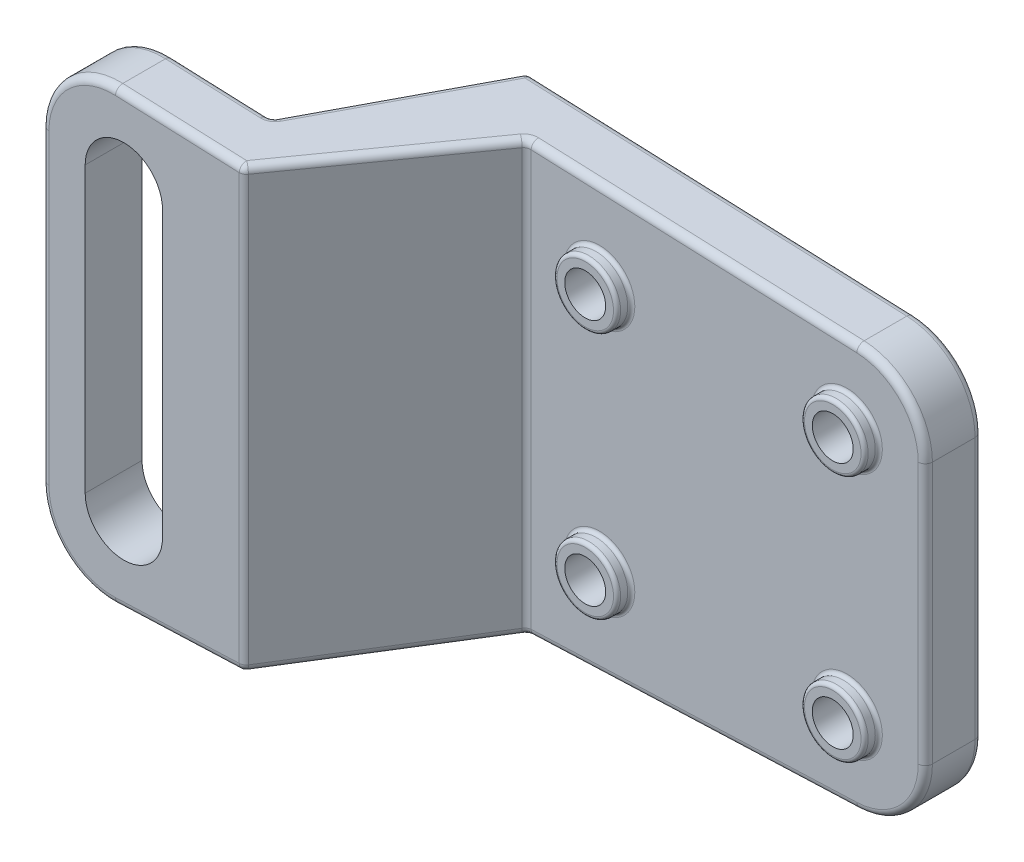
SolidWorks part; units mm, degrees
ref_plane "Front Plane" through (0, 0, 0) normal (0, 0, 1) x (1, 0, 0)
ref_plane "Top Plane" through (0, 0, 0) normal (0, 1, 0) x (1, 0, 0)
ref_plane "Right Plane" through (0, 0, 0) normal (1, 0, 0) x (0, 0, -1)
sketch "Sketch1" plane through (0, 0, 0) normal (0, 0, 1) x (1, 0, 0)
  line L0 (0, 0) -> (13.8229, 0) construction
  line L1 (13.8229, 0) -> (13.8229, -13.8229) construction
  line L2 (13.8229, -13.8229) -> (0, -13.8229) construction
  line L3 (0, -13.8229) -> (0, 0) construction
  line L4 (-17.0322, 1.026) -> (-17.0322, -14.849) construction
  line L5 (-17.0322, 1.026) -> (-17.0322, -14.849) construction
  line L6 (-14.8732, 1.026) -> (-14.8732, -14.849)
  line L7 (-19.1912, 1.026) -> (-19.1912, -14.849)
  line L8 (13.8229, 4.3755) -> (13.8229, 0) construction
  line L9 (-21.6121, 5.7885) -> (18.1984, 4.201)
  line L10 (-21.6121, 5.7885) -> (-21.6121, -19.6115)
  line L11 (-21.6121, -19.6115) -> (18.1984, -18.024)
  line L12 (18.1984, 4.201) -> (18.1984, -18.024)
  line L13 (-21.6121, 5.7885) -> (18.1984, -18.024) construction
  line L14 (-21.6121, -19.6115) -> (18.1984, 4.201) construction
  line L15 (13.8229, 0) -> (18.1984, 0) construction
  line L16 (-17.0322, 3.185) -> (-17.0322, 5.6059) construction
  line L17 (-19.1912, -6.9115) -> (-21.6121, -6.9115) construction
  line L18 (6.9115, 0) -> (6.9115, -13.8229) construction
  line L19 (0.4303, 0) -> (0.4303, -13.8229) construction
  circle A0 centre (0, 0) radius 1.905
  circle A1 centre (13.8229, 0) radius 1.905
  circle A2 centre (13.8229, -13.8229) radius 1.905
  circle A3 centre (0, -13.8229) radius 1.905
  arc A4 (-14.8732, 1.026) -> (-19.1912, 1.026) centre (-17.0322, 1.026) ccw
  arc A5 (-19.1912, -14.849) -> (-14.8732, -14.849) centre (-17.0322, -14.849) ccw
  point P11 (-17.0322, -6.9115)
  point P12 (-17.0322, -6.9115)
  point P13 (0, -6.9115)
  point P18 (-0.3798, -6.9115)
  dimension "D2" = 3.81
  dimension "D5" = 2.159
  dimension "D1" = 13.8229
  dimension "D3" = 15.875
  dimension "D4" = 6.4812
  dimension "D6" = 22.225
  dimension "D7" = 25.4
  dimension "D8" = 17.4625
extrude "Boss-Extrude1" add sketch "Sketch1" along normal blind 3.175
fillet "Fillet1" radius 3.9688 4 edges at (-21.6121, -19.6115, 1.5875) (18.1984, -18.024, 1.5875) (18.1984, 4.201, 1.5875) (-21.6121, 5.7885, 1.5875)
sketch "Sketch2" plane through (0, 0, 3.175) normal (0, 0, 1) x (1, 0, 0)
  circle A0 centre (0, -13.8229) radius 1.905 construction
  circle A1 centre (13.8229, -13.8229) radius 1.905 construction
  circle A2 centre (13.8229, 0) radius 1.905 construction
  circle A3 centre (0, 0) radius 1.905 construction
  circle A4 centre (0, -13.8229) radius 1.905
  circle A5 centre (13.8229, -13.8229) radius 1.905
  circle A6 centre (13.8229, 0) radius 1.905
  circle A7 centre (0, 0) radius 1.905
  circle A8 centre (0, 0) radius 1.143
  circle A9 centre (13.8229, 0) radius 1.143
  circle A10 centre (13.8229, -13.8229) radius 1.143
  circle A11 centre (0, -13.8229) radius 1.143
  dimension "D1" = 2.286
extrude "Boss-Extrude2" add sketch "Sketch2" against normal blind 1.5875
sketch "Sketch4" plane through (0, 0, 3.175) normal (0, 0, 1) x (1, 0, 0)
  circle A0 centre (0, 0) radius 1.778
  circle A1 centre (13.8229, 0) radius 1.778
  circle A2 centre (13.8229, -13.8229) radius 1.778
  circle A3 centre (0, -13.8229) radius 1.778
  circle A4 centre (0, -13.8229) radius 1.143 construction
  circle A5 centre (13.8229, -13.8229) radius 1.143 construction
  circle A6 centre (13.8229, 0) radius 1.143 construction
  circle A7 centre (0, 0) radius 1.143 construction
  circle A8 centre (0, -13.8229) radius 1.143
  circle A9 centre (13.8229, -13.8229) radius 1.143
  circle A10 centre (13.8229, 0) radius 1.143
  circle A11 centre (0, 0) radius 1.143
  dimension "D1" = 3.556
extrude "Boss-Extrude3" add sketch "Sketch4" along normal blind 0.7937
sketch "Sketch5" plane through (0, 0, 3.175) normal (0, 0, -1) x (-1, 0, 0)
  line L0 (4.0266, 5.0873) -> (4.0266, -18.9102)
  line L1 (-14.3878, 4.353) -> (17.4852, 5.624) construction
  line L2 (17.4852, -19.4469) -> (-14.3878, -18.1759) construction
  line L3 (-18.1984, -14.2103) -> (-18.1984, 0.3874) construction
  line L4 (21.6121, 1.6584) -> (21.6121, -15.4813) construction
  line L5 (17.4852, -19.4469) -> (4.0266, -18.9102)
  line L6 (21.6121, 1.6584) -> (21.6121, -15.4813)
  line L7 (4.0266, 5.0873) -> (17.4852, 5.624)
  line L8 (19.1912, 1.026) -> (19.1912, -14.849) construction
  line L9 (14.8732, -14.849) -> (14.8732, 1.026) construction
  line L10 (19.1912, 1.026) -> (19.1912, -14.849)
  line L11 (14.8732, -14.849) -> (14.8732, 1.026)
  arc A0 (17.4852, -19.4469) -> (21.6121, -15.4813) centre (17.6433, -15.4813) ccw construction
  arc A1 (21.6121, 1.6584) -> (17.4852, 5.624) centre (17.6433, 1.6584) ccw construction
  arc A2 (17.4852, -19.4469) -> (21.6121, -15.4813) centre (17.6433, -15.4813) ccw
  arc A3 (21.6121, 1.6584) -> (17.4852, 5.624) centre (17.6433, 1.6584) ccw
  arc A4 (14.8732, -14.849) -> (19.1912, -14.849) centre (17.0322, -14.849) ccw construction
  arc A5 (19.1912, 1.026) -> (14.8732, 1.026) centre (17.0322, 1.026) ccw construction
  arc A6 (14.8732, -14.849) -> (19.1912, -14.849) centre (17.0322, -14.849) ccw
  arc A7 (19.1912, 1.026) -> (14.8732, 1.026) centre (17.0322, 1.026) ccw
  dimension "D1" = 22.225
extrude "Boss-Extrude4" add sketch "Sketch5" against normal blind 9.525
sketch "Sketch6" plane through (0, 0, 0) normal (0, 0, 1) x (1, 0, 0)
  line L0 (-7.2016, 5.2139) -> (-7.2016, -19.0368)
  line L1 (14.3878, 4.353) -> (-4.0266, 5.0873) construction
  line L2 (-4.0266, -18.9102) -> (14.3878, -18.1759) construction
  line L3 (18.1984, -14.2103) -> (18.1984, 0.3874) construction
  line L4 (-21.6121, 1.6584) -> (-21.6121, -15.4813) construction
  line L6 (-21.6121, 1.6584) -> (-21.6121, -15.4813)
  line L14 (-17.4852, 5.624) -> (-4.0266, 5.0873) construction
  line L15 (-4.0266, -18.9102) -> (-17.4852, -19.4469) construction
  line L16 (-17.4852, 5.624) -> (-7.2016, 5.2139)
  line L17 (-7.2016, -19.0368) -> (-17.4852, -19.4469)
  arc A10 (-17.4852, 5.624) -> (-21.6121, 1.6584) centre (-17.6433, 1.6584) ccw construction
  arc A11 (-21.6121, -15.4813) -> (-17.4852, -19.4469) centre (-17.6433, -15.4813) ccw construction
  arc A12 (-17.4852, 5.624) -> (-21.6121, 1.6584) centre (-17.6433, 1.6584) ccw
  arc A13 (-21.6121, -15.4813) -> (-17.4852, -19.4469) centre (-17.6433, -15.4813) ccw
  dimension "D1" = 25.4
extrude "Cut-Extrude1" cut sketch "Sketch6" along normal blind 9.525
chamfer "Chamfer1" distance 4.7625 distance2 9.525 1 edges at (-7.2016, -6.9115, 9.525) first distance on face at (-17.0322, -6.9115, 9.525)
chamfer "Chamfer2" distance 6.35 distance2 9.525 1 edges at (-4.0266, -6.9115, 12.7) first distance on face at (-17.0322, -6.9115, 12.7)
fillet "Fillet2" radius 0.1984 16 edges at (15.7279, -13.8229, 1.5875) (15.7279, -13.8229, 0) (15.6009, -13.8229, 3.175) (15.6009, -13.8229, 3.9688) (15.6009, 0, 3.175) (15.6009, 0, 3.9688) (1.905, -13.8229, 1.5875) (1.905, 0, 1.5875) (15.7279, 0, 1.5875) (15.7279, 0, 0) (1.905, 0, 0) (1.905, -13.8229, 0) (1.778, 0, 3.9688) (1.778, 0, 3.175) (1.778, -13.8229, 3.9688) (1.778, -13.8229, 3.175)
fillet "Fillet3" radius 0.3969 28 edges at (3.5931, -18.6064, 0) (17.0914, -16.9602, 0) (18.1984, -6.9115, 0) (17.0914, 3.1372, 0) (3.5931, 4.7834, 0) (5.1806, 4.7201, 3.175) (17.0914, 3.1372, 3.175) (18.1984, -6.9115, 3.175) (17.0914, -16.9602, 3.175) (5.1806, -18.5431, 3.175) (-14.7246, 5.5139, 9.525) (-14.7246, -19.3368, 9.525) (-20.3932, -18.343, 9.525) (-21.6121, -6.9115, 9.525) (-13.9309, -19.3052, 12.7) (-20.3932, -18.343, 12.7) (-21.6121, -6.9115, 12.7) (-13.9309, 5.4822, 12.7) (-7.2016, -6.9115, 0) (-9.5828, 5.3088, 4.7625) (-11.9641, -6.9115, 9.525) (-9.5828, -19.1318, 4.7625) (-20.3932, 4.5201, 9.525) (-20.3932, 4.5201, 12.7) (-4.0266, -6.9115, 3.175) (-7.2016, -19.0368, 7.9375) (-10.3766, -6.9115, 12.7) (-7.2016, 5.2139, 7.9375)
